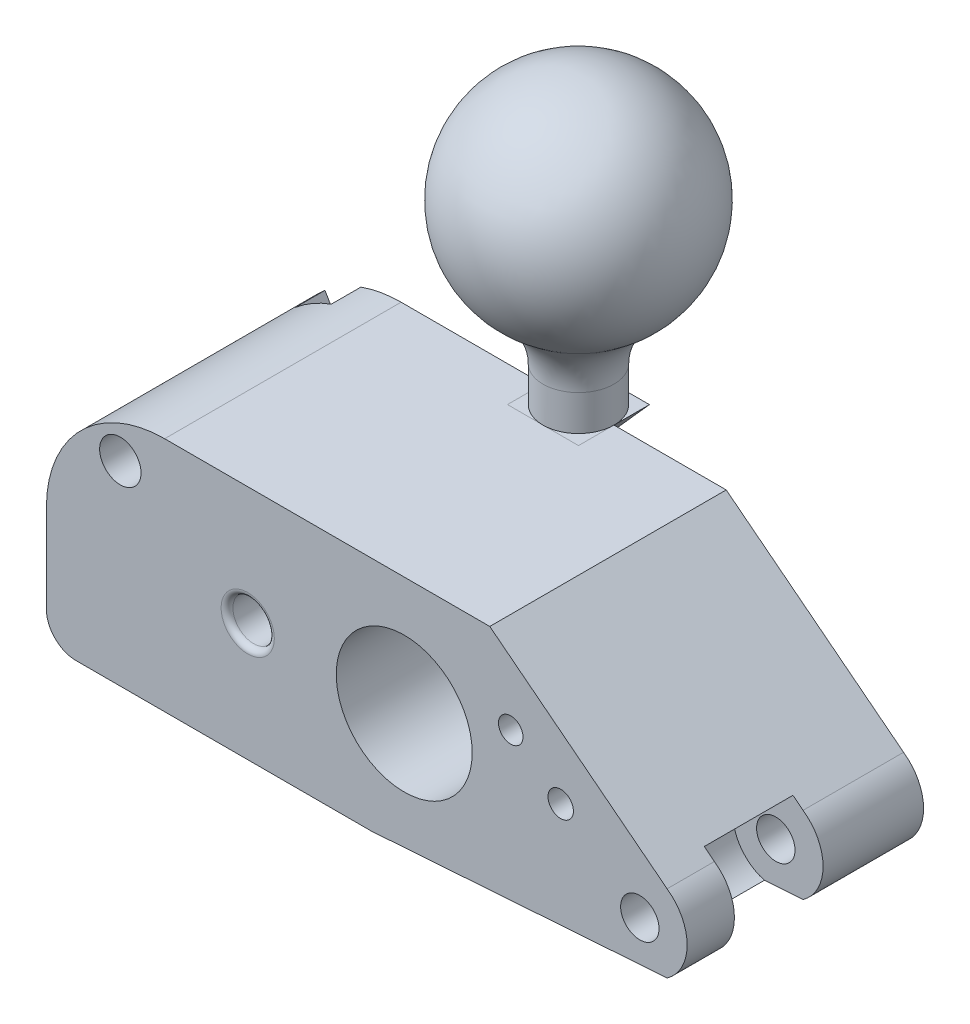
SolidWorks part; units mm, degrees
ref_plane "Front Plane" through (0, 0, 0) normal (0, 0, 1) x (1, 0, 0)
ref_plane "Top Plane" through (0, 0, 0) normal (0, 1, 0) x (1, 0, 0)
ref_plane "Right Plane" through (0, 0, 0) normal (1, 0, 0) x (0, 0, -1)
sketch "Sketch1" plane through (0, 0, 0) normal (0, 0, 1) x (1, 0, 0)
  line L0 (0, 0) -> (0, -18.415) construction
  line L3 (-3.2761, -9.2075) -> (3.2761, -9.2075) construction
  line L5 (-15.9479, -9.2075) -> (-15.9479, -5.9187) construction
  line L6 (15.9313, -9.2362) -> (15.9313, 2.2858) construction
  line L7 (0, -18.415) -> (0, 18761.3337) construction
  line L13 (15.9489, -30) -> (15.9313, -9.2362) construction
  line L14 (-15.9479, -9.2075) -> (-15.9655, -30) construction
  line L23 (0, 0) -> (-50, 0) construction
  line L24 (15.9489, -30) -> (-30, -30)
  line L27 (-50, -50) -> (-50, -65)
  line L28 (-15.9655, -30) -> (55, -30)
  line L30 (-45, -70) -> (55, -70)
  line L31 (55, -30) -> (55, -70)
  line L32 (15.9489, -30) -> (-15.9655, -30)
  line L36 (-50, 0) -> (-50, -30) construction
  line L38 (-40, -50) -> (-40, -56) construction
  line L39 (-40, -50) -> (-40, -56) construction
  line L90 (0, 18.415) -> (0, -18.415)
  line L160 (-6.0083, -6.83) -> (6.0083, -6.83) construction
  line L161 (-6.0083, -6.83) -> (-6.0083, -30) construction
  line L162 (-6.0083, -30) -> (6.0083, -30) construction
  line L163 (6.0083, -6.83) -> (6.0083, -30) construction
  line L166 (-6.0083, -6.83) -> (-0.0083, -6.83)
  line L178 (-6.0083, -6.83) -> (-6.0083, -30)
  line L179 (-6.0083, -6.83) -> (6.0083, -30) construction
  line L180 (-6.0083, -30) -> (6.0083, -6.83) construction
  line L181 (-6.0083, -30) -> (-0.0083, -30)
  line L182 (-0.0083, -6.83) -> (-0.0083, -30)
  circle A0 centre (0, 0) radius 18.415 construction
  arc A1 (-30, -30) -> (-50, -50) centre (-30, -50) ccw
  arc A2 (-30, -40) -> (-40, -50) centre (-30, -50) ccw construction
  arc A3 (-40, -50) -> (-30, -40) centre (-30, -50) cw construction
  arc A12 (-50, -65) -> (-45, -70) centre (-45, -65) ccw
  arc A51 (0, -18.415) -> (0, 18.415) centre (0, 0) cw
  point P6 (0, -9.2075)
  point P30 (-37.0711, -42.9289)
  point P36 (-40, -52.5365)
  point P45 (-50, -70)
  dimension "D2" = 36.83
  dimension "D6" = 20
  dimension "D9" = 5
  dimension "D14" = 31.8791
  dimension "D1" = 30
  dimension "D3" = 50
  dimension "D5" = 40
  dimension "D12" = 70.9655
  dimension "D13" = 100
  dimension "D15" = 6
  dimension "D17" = 6
  dimension "D7" = 10
extrude "Boss-Extrude1" add sketch "Sketch1" along normal blind 40 contours L27 A12 L24 A1 region at (3.5706, -50.2999, 0)
sketch "Sketch4" plane through (0, 0, 0) normal (0, 0, -1) x (-1, 0, 0)
  line L0 (15.9479, -50) -> (-5, -50) construction
  line L5 (7.4479, -45.0925) -> (7.4479, -54.9075)
  line L6 (7.4479, -54.9075) -> (15.9479, -59.815)
  line L7 (15.9479, -59.815) -> (24.4479, -54.9075)
  line L8 (24.4479, -54.9075) -> (24.4479, -45.0925)
  line L9 (24.4479, -45.0925) -> (15.9479, -40.185)
  line L10 (7.4479, -45.0925) -> (-6.0083, -30)
  line L11 (-6.0083, -30) -> (6.0083, -30)
  line L12 (6.0083, -30) -> (15.9479, -40.185)
  line L14 (15.9479, -40.185) -> (11.6979, -42.6388) [skipped]
  arc A0 (7.4479, -50) -> (20.1979, -42.6388) centre (15.9479, -50) ccw construction
  dimension "D1" = 17
revolve "Revolve8" add sketch "Sketch1<7>" angle 360 about L90
sketch "Sketch1<7>" plane through (0, 0, 0) normal (0, 0, 1) x (1, 0, 0) same geometry as "Sketch1"
fillet "Fillet3" radius 11 1 edges at (0, -17.4072, 6.0083)
extrude "Boss-Extrude3" add sketch "Sketch4" along normal blind 6 and the other way blind 6
extrude "Cut-Extrude2" cut sketch "Sketch4<2>" against normal blind 6
sketch "Sketch4<2>" plane through (0, 0, 0) normal (0, 0, -1) x (-1, 0, 0) same geometry as "Sketch4"
sketch "Sketch14" plane through (0, 0, 0) normal (0, 0, -1) x (-1, 0, 0)
  line L0 (24, -42.25) -> (30, -42.1947)
  line L1 (37.75, -56) -> (37.75, -50.9271)
  arc A0 (37.75, -50.9271) -> (30, -42.1947) centre (30.0713, -49.9367) ccw
  arc A1 (24, -42.25) -> (37.75, -56) centre (47.3341, -32.6659) ccw
extrude "Cut-Extrude8" [suppressed] cut sketch "Sketch14" against normal blind 3 contours A1 L1 A0 L0
fillet "Fillet7" [suppressed] radius 1
sketch "Sketch15" plane through (0, 0, 6) normal (0, 0, -1) x (-1, 0, 0)
  line L0 (20.1979, -42.6388) -> (11.6979, -57.3612) construction
  line L3 (7.4479, -50) -> (24.4479, -50) construction
  line L6 (20.1979, -57.3612) -> (11.6979, -42.6388) construction
  circle A0 centre (15.9479, -50) radius 2.15
  circle A1 centre (15.9479, -50) radius 3.5
  dimension "D1" = 4.3
  dimension "D2" = 7
extrude "Cut-Extrude9" cut sketch "Sketch15" against normal blind 14 contours A0
extrude "Cut-Extrude10" cut sketch "Sketch15<5>" against normal blind 24 from offset 14 contours A0 | A1 A0 region at (-15.9479, -50, 6) region at (-12.5469, -50, 6) offset against normal yes
sketch "Sketch15<5>" plane through (0, 0, 6) normal (0, 0, -1) x (-1, 0, 0) same geometry as "Sketch15"
fillet "Fillet8" radius 1 1 edges at (-12.4479, -50, 40)
sketch "Sketch16" plane through (55, 0, 0) normal (1, 0, 0) x (0, 0, -1)
  line L12 (-17.171, -33.4404) -> (-22.829, -33.4404)
  line L13 (-25.2283, -30.75) -> (-36.5477, -30.75)
  line L14 (-39.25, -33.4542) -> (-39.25, -44.7717)
  line L15 (-36.5596, -47.171) -> (-36.5596, -52.829)
  line L16 (-39.25, -55.2283) -> (-39.25, -66.5478)
  line L17 (-36.5458, -69.25) -> (-25.2283, -69.25)
  line L18 (-22.829, -66.5596) -> (-17.171, -66.5596)
  line L19 (-14.7717, -69.25) -> (-3.4522, -69.25)
  line L20 (-0.75, -66.5458) -> (-0.75, -55.2283)
  line L21 (-3.4404, -52.829) -> (-3.4404, -47.171)
  line L22 (-0.75, -44.7717) -> (-0.75, -33.4522)
  line L23 (-3.4542, -30.75) -> (-14.7717, -30.75)
  line L24 (-20, -33.4404) -> (-20, -66.5596) construction
  line L25 (-20, -30) -> (-20, -70) construction
  line L26 (-40, -30) -> (0, -30) construction
  line L27 (-40, -70) -> (0, -70) construction
  line L28 (-40, -50) -> (0, -50) construction
  line L29 (-40, -30) -> (-40, -70) construction
  line L30 (0, -30) -> (0, -70) construction
  arc A20 (-23.8286, -32.4703) -> (-22.829, -33.4404) centre (-22.829, -32.4404) ccw
  arc A21 (-23.8286, -32.4703) -> (-25.2283, -30.75) centre (-25.6526, -32.5248) ccw
  arc A22 (-36.5477, -30.75) -> (-39.25, -33.4542) centre (-35.9313, -34.0682) ccw
  arc A23 (-39.25, -44.7717) -> (-37.5297, -46.1714) centre (-37.4752, -44.3474) ccw
  arc A24 (-36.5596, -47.171) -> (-37.5297, -46.1714) centre (-37.5596, -47.171) ccw
  arc A25 (-37.5297, -53.8286) -> (-36.5596, -52.829) centre (-37.5596, -52.829) ccw
  arc A26 (-37.5297, -53.8286) -> (-39.25, -55.2283) centre (-37.4752, -55.6526) ccw
  arc A27 (-39.25, -66.5478) -> (-36.5458, -69.25) centre (-35.9318, -65.9313) ccw
  arc A28 (-25.2283, -69.25) -> (-23.8286, -67.5297) centre (-25.6526, -67.4752) ccw
  arc A29 (-22.829, -66.5596) -> (-23.8286, -67.5297) centre (-22.829, -67.5596) ccw
  arc A30 (-16.1714, -67.5297) -> (-17.171, -66.5596) centre (-17.171, -67.5596) ccw
  arc A31 (-16.1714, -67.5297) -> (-14.7717, -69.25) centre (-14.3474, -67.4752) ccw
  arc A32 (-3.4522, -69.25) -> (-0.75, -66.5458) centre (-4.0687, -65.9318) ccw
  arc A33 (-0.75, -55.2283) -> (-2.4703, -53.8286) centre (-2.5248, -55.6526) ccw
  arc A34 (-3.4404, -52.829) -> (-2.4703, -53.8286) centre (-2.4404, -52.829) ccw
  arc A35 (-2.4703, -46.1714) -> (-3.4404, -47.171) centre (-2.4404, -47.171) ccw
  arc A36 (-2.4703, -46.1714) -> (-0.75, -44.7717) centre (-2.5248, -44.3474) ccw
  arc A37 (-0.75, -33.4522) -> (-3.4542, -30.75) centre (-4.0682, -34.0687) ccw
  arc A38 (-14.7717, -30.75) -> (-16.1714, -32.4703) centre (-14.3474, -32.5248) ccw
  arc A39 (-17.171, -33.4404) -> (-16.1714, -32.4703) centre (-17.171, -32.4404) ccw
  point P54 (-20, -50)
sketch "Sketch17" plane through (0, 0, 40) normal (0, 0, 1) x (1, 0, 0)
  line L0 (55, -50) -> (37, -50) construction
  line L2 (42.1962, -50) -> (39.5981, -45.5)
  line L3 (39.5981, -45.5) -> (34.4019, -45.5)
  line L4 (34.4019, -45.5) -> (31.8038, -50)
  line L5 (31.8038, -50) -> (34.4019, -54.5)
  line L6 (34.4019, -54.5) -> (39.5981, -54.5)
  line L7 (39.5981, -54.5) -> (42.1962, -50)
  circle A0 centre (37, -50) radius 2.15
  circle A1 centre (37, -50) radius 4.5 construction
  dimension "D2" = 4.3
  dimension "D3" = 9
  dimension "D1" = 18
extrude "Cut-Extrude12" cut sketch "Sketch17" against normal blind 57 contours A0
extrude "Cut-Extrude13" cut sketch "Sketch17<4>" against normal blind 3.7 from offset 10 contours L3 L4 L5 L6 L7 L2 offset against normal yes
sketch "Sketch17<4>" plane through (0, 0, 40) normal (0, 0, 1) x (1, 0, 0) same geometry as "Sketch17"
chamfer "Chamfer1" distance 30 angle 38 1 edges at (55, -30, 20) first distance on face at (6.25, -30, 11.5)
chamfer "Chamfer2" distance 50 angle 4 1 edges at (55, -70, 20) first distance on face at (5, -70, 20)
sketch "Sketch20" plane through (0, 0, 40) normal (0, 0, 1) x (1, 0, 0)
  arc A0 (55, -53.4386) -> (55, -66.5037) centre (50.382, -59.9711) cw
  circle A1 centre (50.382, -59.9711) radius 3.25
  line M13 (55, -66.5037) -> (55, -53.4386)
  dimension "D1" = 8
  dimension "D2" = 6.5
extrude "Boss-Extrude4" add sketch "Sketch20" against normal up to surface (40 mm away) contours A1 A0 M13 region at (56.3808, -59.9711, 40) up to face at (39.15, -50, 0)
extrude "Cut-Extrude14" cut sketch "Sketch20<3>" against normal up to surface (40 mm away) contours A1 up to face at (39.15, -50, 0)
sketch "Sketch20<3>" plane through (0, 0, 40) normal (0, 0, 1) x (1, 0, 0) same geometry as "Sketch20"
sketch "Sketch21" plane through (0, 0, 0) normal (0, 1, 0) x (1, 0, 0)
  line L0 (-30, -40) -> (25, -40) construction
  line L1 (25, 0) -> (6.0083, 0) construction
  line L2 (6.0083, 0) -> (6.0083, -6) construction
  line L3 (6.0083, -6) -> (-6.0083, -6) construction
  line L4 (-6.0083, -6) -> (-6.0083, 0) construction
  line L5 (-6.0083, 0) -> (-30, 0) construction
  line L8 (-30, 0) -> (-30, -40) construction
  line L9 (25, -40) -> (55, -40) construction
  line L10 (55, 0) -> (25, 0) construction
  line L11 (55, -40) -> (55, 0) construction
  line L12 (58.382, 0) -> (55, 0) construction
  line L13 (55, -40) -> (58.382, -40) construction
  line L14 (-30, -40) -> (25, -40)
  line L15 (25, 0) -> (6.0083, 0)
  line L16 (6.0083, 0) -> (6.0083, -6)
  line L17 (6.0083, -6) -> (-6.0083, -6)
  line L18 (-6.0083, -6) -> (-6.0083, 0)
  line L19 (-6.0083, 0) -> (-30, 0)
  line L22 (-30, 0) -> (-30, -40)
  line L23 (25, -40) -> (55, -40)
  line L24 (55, 0) -> (25, 0)
  line L25 (55, -40) -> (55, 0)
  line L26 (58.382, 0) -> (55, 0)
  line L27 (55, -40) -> (58.382, -40)
  line L28 (54.382, -40) -> (54.382, -32) construction
  line L29 (54.382, -32) -> (54.382, -17) construction
  line L30 (54.382, -17) -> (54.382, -13) construction
  line L31 (40, -40) -> (40, -10) construction
  line L32 (54.382, -24.5) -> (58.382, -24.5) construction
  line L34 (50.382, -32) -> (58.382, -32)
  line L35 (50.382, -32) -> (50.382, -17)
  line L36 (50.382, -17) -> (58.382, -17)
  line L37 (58.382, -32) -> (58.382, -17)
  line L38 (50.382, -32) -> (58.382, -17) construction
  line L39 (50.382, -17) -> (58.382, -32) construction
  line L40 (58.382, -40) -> (58.382, 0) construction
  point P17 (54.382, -24.5)
  dimension "D1" = 8
  dimension "D2" = 15
  dimension "D3" = 30
  dimension "D4" = 4
  dimension "D5" = 4
  dimension "D6" = 8
extrude "Cut-Extrude15" [suppressed] cut sketch "Sketch21" against normal blind 85.7 contours L34 L37 L36 L25 | L35 L34 L37 L36
sketch "Sketch22" plane through (0, 0, 40) normal (0, 0, 1) x (1, 0, 0)
  line L0 (49.1231, -52.8313) -> (67.8517, -49.5289)
  line L1 (56.8772, -59.9711) -> (53.6296, -54.3461)
  line L2 (53.6296, -54.3461) -> (47.1344, -54.3461)
  line L3 (47.1344, -54.3461) -> (43.8868, -59.9711)
  line L4 (43.8868, -59.9711) -> (47.1344, -65.5961)
  line L5 (47.1344, -65.5961) -> (53.6296, -65.5961)
  line L6 (53.6296, -65.5961) -> (56.8772, -59.9711)
  line L7 (49.1231, -67.111) -> (67.8517, -70.4133)
  line L8 (67.8517, -52.7211) -> (80.382, -52.7211)
  line L10 (67.8517, -67.2211) -> (80.382, -67.2211)
  line L11 (80.382, -52.7211) -> (80.382, -67.2211)
  line L12 (67.8517, -70.4133) -> (67.8517, -49.5289)
  circle A0 centre (50.382, -59.9711) radius 5.625 construction
  circle A3 centre (50.382, -59.9711) radius 7.25
  arc A4 (49.1231, -52.8313) -> (49.1231, -67.111) centre (50.382, -59.9711) ccw
  point P0 (0, 0)
  point P10 (50.382, -59.9711)
  point P20 (0, 0)
  line M13 (5, -70) -> (55, -66.5037)
  arc M14 (55, -66.5037) -> (55, -53.4386) centre (50.382, -59.9711) ccw
  line M15 (55, -53.4386) -> (25, -30)
  circle M20 centre (50.382, -59.9711) radius 3.25
  dimension "D1" = 11.25
  dimension "D4" = 10
  dimension "D5" = 10
  dimension "D6" = 20.8844
  dimension "D8" = 14.5
  dimension "D2" = 4
extrude "Cut-Extrude16" cut sketch "Sketch22" against normal blind 15 from offset 8 contours A4 L7 L12 L0 M13 M15 M14 | L5 L6 L1 L2 L3 L4 M20 | L0 A4 L6 L5 L4 L3 L2 L1 M13 M14 M15 region at (51.2333, -52.6341, 40) region at (54.9116, -54.573, 40) region at (62.2465, -60.0634, 40) region at (50.8706, -66.9577, 40) region at (55.1046, -62.6977, 40) offset against normal yes
extrude "Cut-Extrude17" cut sketch "Sketch22<3>" against normal blind 4.4 from offset 28 contours L2 L3 L4 L5 L6 L1 offset against normal yes
sketch "Sketch22<3>" plane through (0, 0, 40) normal (0, 0, 1) x (1, 0, 0) same geometry as "Sketch22"
sketch "Sketch24" plane through (0, 0, 40) normal (0, 0, 1) x (1, 0, 0)
  line L0 (-30, -50) -> (-30, -35) construction
  line L1 (-30, -50) -> (-37.5, -37.0096) construction
  line L2 (-40.5311, -38.7596) -> (-34.4689, -35.2596)
  line L3 (-40.5311, -38.7596) -> (-46.5311, -28.3673)
  line L4 (-34.4689, -35.2596) -> (-40.4689, -24.8673)
  line L5 (-46.5311, -28.3673) -> (-40.4689, -24.8673)
  circle A1 centre (-37.5, -37.0096) radius 2.15
  arc A2 (-30, -35) -> (-45, -50) centre (-30, -50) ccw
  arc A3 (-30, -35) -> (-45, -50) centre (-30, -50) ccw
  circle A4 centre (-37.5, -37.0096) radius 3.5
  dimension "D3" = 4.3
  dimension "D4" = 7
  dimension "D2" = 30
  dimension "D5" = 12
  dimension "D1" = 5
extrude "Cut-Extrude18" cut sketch "Sketch24" against normal blind 5 and the other way blind 5 from surface contours A3 A4 A1 | A1 A3 | A3 A4 L2 A1 | A3 A1 L2 | L2 A4 A3 A1 | A3 L2 A1 | L4 L5 L3 L2 region at (-39.961, -38.5986, 40) region at (-38.8726, -37.8555, 40) region at (-34.8934, -35.6729, 40) region at (-39.7511, -38.7071, 40) region at (-36.0811, -36.2438, 40) region at (-37.0302, -37.8234, 40) starting at face at (53.632, -59.9711, 0)
extrude "Cut-Extrude19" cut sketch "Sketch24<4>" against normal blind 22 contours A4
sketch "Sketch24<4>" plane through (0, 0, 40) normal (0, 0, 1) x (1, 0, 0) same geometry as "Sketch24"
extrude "Cut-Extrude20" cut sketch "Sketch24<6>" against normal blind 42 contours A1
sketch "Sketch24<6>" plane through (0, 0, 40) normal (0, 0, 1) x (1, 0, 0) same geometry as "Sketch24"
sketch "Sketch27" plane through (0, 0, 40) normal (0, 0, 1) x (1, 0, 0)
  line L0 (-15.9479, -50) -> (37, -50) construction
  line L1 (25, -30) -> (10.5261, -50) construction
  line L2 (37, -50) -> (20.0882, -36.7871) construction
  line L3 (55, -53.4386) -> (25, -30) construction
  circle A0 centre (10.5261, -50) radius 11.5
  circle A1 centre (10.5261, -50) radius 3.1
  circle A2 centre (28.5441, -43.3935) radius 2.075
  dimension "D1" = 23
  dimension "D2" = 6.2
  dimension "D3" = 4.15
extrude "Cut-Extrude21" cut sketch "Sketch27" along normal blind 15 from surface contours A1 starting at face at (53.632, -59.9711, 0)
extrude "Cut-Extrude22" cut sketch "Sketch27<3>" against normal up to surface (25 mm away) contours A0 up to face at (13.6261, -50, 15)
sketch "Sketch27<3>" plane through (0, 0, 40) normal (0, 0, 1) x (1, 0, 0) same geometry as "Sketch27"
extrude "Cut-Extrude23" cut sketch "Sketch27<5>" against normal blind 20 contours A2
sketch "Sketch27<5>" plane through (0, 0, 40) normal (0, 0, 1) x (1, 0, 0) same geometry as "Sketch27"
